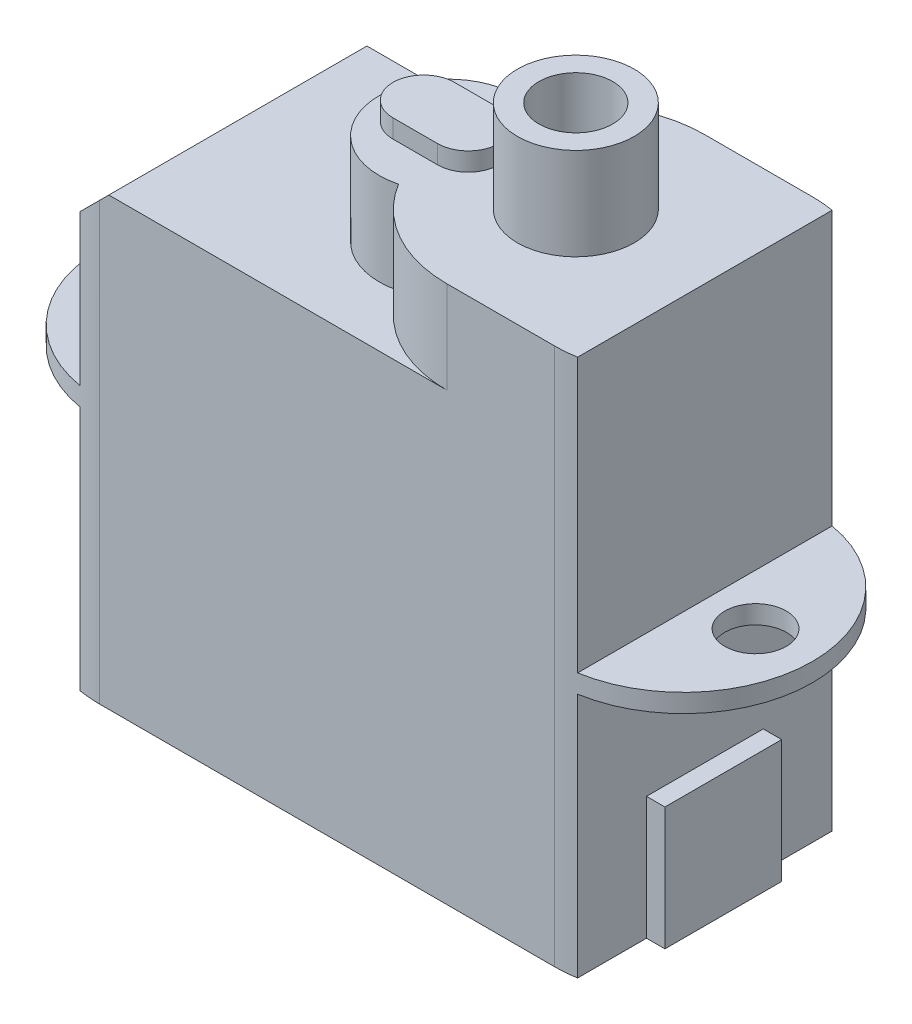
SolidWorks part; units mm, degrees
ref_plane "Front Plane" through (0, 0, 0) normal (0, 0, 1) x (1, 0, 0)
ref_plane "Top Plane" through (0, 0, 0) normal (0, 1, 0) x (1, 0, 0)
ref_plane "Right Plane" through (0, 0, 0) normal (1, 0, 0) x (0, 0, -1)
sketch "Sketch1" plane through (0, 0, 0) normal (0, 1, 0) x (1, 0, 0)
  line L1 (-8.1, -4.2) -> (8.1, -4.2)
  line L2 (-8.1, -4.2) -> (-8.1, 4.2)
  line L3 (-8.1, 4.2) -> (8.1, 4.2)
  line L4 (8.1, -4.2) -> (8.1, 4.2)
  line L5 (-8.1, -4.2) -> (8.1, 4.2) construction
  line L6 (-8.1, 4.2) -> (8.1, -4.2) construction
  point P0 (0, 0)
  dimension "D1" = 16.2
  dimension "D2" = 8.4
extrude "Boss-Extrude1" add sketch "Sketch1" along normal blind 14.5
sketch "Sketch3" plane through (0, 14.5, 0) normal (0, 1, 0) x (1, 0, 0)
  line L0 (8.1, 4.2) -> (-8.1, 4.2) construction
  line L1 (8.1, -4.2) -> (8.1, 4.2) construction
  line L2 (-8.1, -4.2) -> (8.1, -4.2) construction
  line L3 (3.9, 4.2) -> (8.1, 4.2)
  line L4 (8.1, 4.2) -> (8.1, -4.2)
  line L5 (8.1, -4.2) -> (3.9, -4.2)
  circle A0 centre (3.9, 0) radius 1.9
  arc A1 (3.9, 4.2) -> (0.3096, 2.1793) centre (3.9, 0) ccw
  arc A2 (0.3096, 2.1793) -> (0.3096, -2.1793) centre (-0.25, 0) ccw
  arc A3 (0.3096, -2.1793) -> (3.9, -4.2) centre (3.9, 0) ccw
  dimension "D1" = 3.8
  dimension "D2" = 4.5
  dimension "D3" = 8.35
extrude "Boss-Extrude2" add sketch "Sketch3" along normal blind 3 contours L3 L4 L5 A3 A2 A1 | A0
extrude "Boss-Extrude3" add sketch "Sketch3<3>" along normal blind 6 contours A0 region at (3.9, 14.5, 0)
sketch "Sketch3<3>" plane through (0, 14.5, 0) normal (0, 1, 0) x (1, 0, 0) same geometry as "Sketch3"
ref_plane "Plane1" through (0, 8, 0) normal (0, 1, 0) x (1, 0, 0)
sketch "Sketch6" plane through (0, 8, 0) normal (0, 1, 0) x (1, 0, 0)
  line L0 (3.9, 4.2) -> (8.1, 4.2) construction
  line L1 (8.1, -4.2) -> (11.6, -4.2)
  line L2 (8.1, -4.2) -> (8.1, 4.2)
  line L3 (8.1, 4.2) -> (11.6, 4.2)
  line L4 (11.6, -4.2) -> (11.6, 4.2)
  line L5 (0, -4.62) -> (0, 4.62) construction
  line L6 (-8.1, 4.2) -> (-11.6, 4.2)
  line L7 (-11.6, -4.2) -> (-11.6, 4.2)
  line L8 (-8.1, -4.2) -> (-11.6, -4.2)
  line L9 (-8.1, -4.2) -> (-8.1, 4.2)
  circle A0 centre (9.75, 0) radius 1
  circle A1 centre (-9.75, 0) radius 1
  dimension "D2" = 2
  dimension "D1" = 3.5
  dimension "D3" = 19.5
extrude "Boss-Extrude4" add sketch "Sketch6" along normal blind 0.6
fillet "Fillet2" 2 edges at (11.6, 8.3, 4.2) (11.6, 8.3, -4.2) type full round first side face at (0.5571, 9.3143, 4.2) second side face at (0.5571, 9.3143, -4.2) middle face at (11.6, 8.3, 0)
fillet "Fillet3" 2 edges at (-11.6, 8.3, 4.2) (-11.6, 8.3, -4.2) type full round first side face at (-1.5167, 9.4833, 4.2) second side face at (-1.5167, 9.4833, -4.2) middle face at (-11.6, 8.3, 0)
sketch "Sketch7" plane through (0, 17.5, 0) normal (0, 1, 0) x (1, 0, 0)
  line L0 (-1.05, 0) -> (0.4, 0) construction
  line L1 (-1.05, 1) -> (0.4, 1)
  line L2 (-1.05, -1) -> (0.4, -1)
  arc A0 (-1.05, 1) -> (-1.05, -1) centre (-1.05, 0) ccw
  arc A1 (0.4, -1) -> (0.4, 1) centre (0.4, 0) ccw
  circle A2 centre (3.9, 0) radius 1.9 construction
  arc A3 (0.3096, 2.1793) -> (0.3096, -2.1793) centre (-0.25, 0) ccw construction
  point P3 (-0.325, 0)
  dimension "D2" = 3.5
  dimension "D3" = 0.8
  dimension "D1" = 2
extrude "Boss-Extrude5" add sketch "Sketch7" along normal blind 0.6
sketch "Sketch8" plane through (8.1, 0, 0) normal (1, 0, 0) x (0, 0, -1)
  line L0 (-4.1413, 0) -> (4.1413, 0) construction
  line L1 (-1.9, 0) -> (1.9, 0)
  line L2 (-1.9, 0) -> (-1.9, 4)
  line L3 (-1.9, 4) -> (1.9, 4)
  line L4 (1.9, 0) -> (1.9, 4)
  dimension "D1" = 3.8
  dimension "D2" = 4
extrude "Boss-Extrude6" add sketch "Sketch8" along normal blind 0.6
chamfer "Chamfer1" distance 1 angle 45 1 edges at (-8.1, 14.5, 0)
hole_wizard "M2 Clearance Hole1" positions "Sketch9" profile "Sketch10" hole size "M2" standard "ISO"
sketch "Sketch9" plane through (0, 20.5, 0) normal (0, 1, 0) x (1, 0, 0)
  circle A0 centre (3.9, 0) radius 1.9 construction
  point P0 (3.9, 0)
sketch "Sketch10" plane through (3.9, 20.5, 0) normal (1, 0, 0) x (0, 0, 1)
  line L0 (0, 0) -> (0, 6.721)
  line L1 (0, 6.721) -> (1.2, 6)
  line L2 (1.2, 6) -> (1.2, 0)
  line L5 (1.2, 0) -> (0, 0)
  line L10 (0, 6.721) -> (-1.2, 6) construction
  line L11 (0, -6.35) -> (0, 107.95) construction
  dimension "Hole Dia." = 2.4
  dimension "Hole Depth" = 6
  dimension "Drill Angle" = 118
